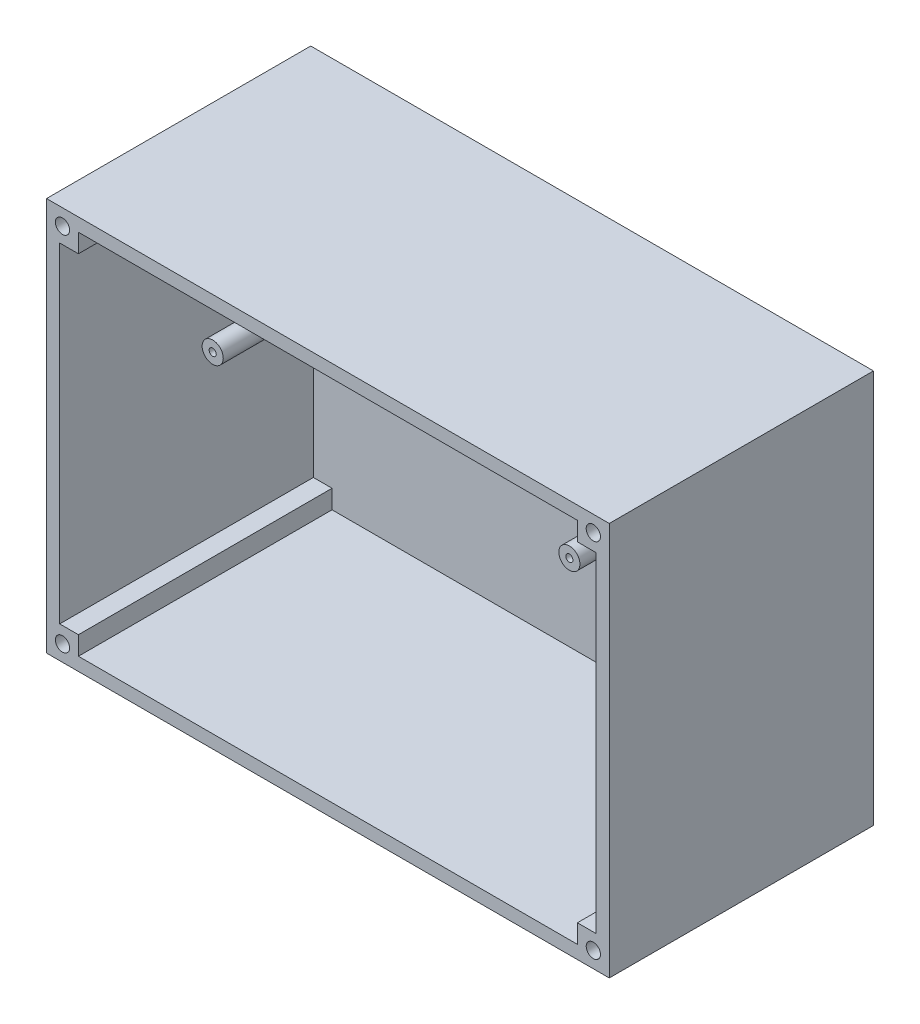
SolidWorks part; units mm, degrees
ref_plane "Płaszczyzna przednia" through (0, 0, 0) normal (0, 0, 1) x (1, 0, 0)
ref_plane "Płaszczyzna górna" through (0, 0, 0) normal (0, 1, 0) x (1, 0, 0)
ref_plane "Płaszczyzna prawa" through (0, 0, 0) normal (1, 0, 0) x (0, 0, -1)
sketch "Szkic4" plane through (0, 0, 0) normal (0, 0, 1) x (-1, 0, 0)
  line L26 (-171.4939, -76.4107) -> (31.5061, -76.4107)
  line L30 (-171.4939, -76.4107) -> (-171.4939, 62.5893)
  line L34 (31.5061, 0) -> (31.5061, -76.4107)
  line L35 (31.5061, 0) -> (31.5061, 62.5893)
  line L36 (31.5061, 62.5893) -> (-171.4939, 62.5893)
  point P86 (-69.4627, -6.9107)
sketch "Szkic5" plane through (0, 0, 0) normal (0, 0, 1) x (-1, 0, 0)
  line L26 (-171.4939, -76.4107) -> (31.5061, -76.4107)
  line L30 (-171.4939, -76.4107) -> (-171.4939, 62.5893)
  line L33 (30.0061, 0) -> (31.5061, 0)
  line L34 (31.5061, 0) -> (31.5061, -76.4107)
  line L35 (31.5061, 0) -> (31.5061, 62.5893)
  line L36 (31.5061, 62.5893) -> (-171.4939, 62.5893)
  line L37 (-176.4939, 67.5893) -> (36.5061, 67.5893)
  line L38 (36.5061, 67.5893) -> (36.5061, -81.4107)
  line L39 (36.5061, -81.4107) -> (-176.4939, -81.4107)
  line L40 (-176.4939, -81.4107) -> (-176.4939, 67.5893)
  circle A0 centre (-154.7539, 47.5493) radius 1.35
  circle A1 centre (-154.7539, -0.7107) radius 1.35
  circle A2 centre (-103.9539, 14.5293) radius 1.35
  circle A3 centre (-103.9539, 42.4693) radius 1.35
  circle A12 centre (-149.9208, -27.9486) radius 1.35
  circle A13 centre (-149.9208, -54.9486) radius 1.35
  circle A14 centre (-149.9208, -27.9486) radius 3.5
  circle A15 centre (-149.9208, -54.9486) radius 3.5
  circle A16 centre (-154.7539, -0.7107) radius 3.5
  circle A17 centre (-154.7539, 47.5493) radius 3.5
  circle A18 centre (-103.9539, 42.4693) radius 3.5
  circle A19 centre (-103.9539, 14.5293) radius 3.5
  circle A28 centre (-121.3881, -22.5) radius 4
  circle A29 centre (-121.3881, -22.5) radius 1.35
  circle A30 centre (-121.3881, -69.5) radius 1.35
  circle A31 centre (-121.3881, -69.5) radius 4
  circle A32 centre (13.6119, -22.5) radius 1.35
  circle A33 centre (13.6119, -69.5) radius 1.35
  circle A34 centre (13.6119, -69.5) radius 4
  circle A35 centre (13.6119, -22.5) radius 4
  point P1 (0, 0)
  point P86 (-69.4627, -6.9107)
  dimension "D2" = 2.7
  dimension "D3" = 2.7
  dimension "D6" = 2.7
  dimension "D7" = 2.7
  dimension "D8" = 2.7
  dimension "D9" = 2.7
  dimension "D10" = 2.7
  dimension "D11" = 2.7
  dimension "D12" = 2.7
  dimension "D13" = 2.7
  dimension "D14" = 7
  dimension "D15" = 7
  dimension "D16" = 7
  dimension "D17" = 7
  dimension "D18" = 8
  dimension "D19" = 8
  dimension "D20" = 8
  dimension "D21" = 8
  dimension "D22" = 7
  dimension "D23" = 7
  dimension "D33" = 213
  dimension "D34" = 149
extrude "Dodanie-wyciągnięcie1" add sketch "Szkic5" along normal blind 100 contours L40 L39 L38 L37 L36 L35 L34 L26 L30 region at (69.9939, -64.9899, 0)
extrude "Dodanie-wyciągnięcie2" add sketch "Szkic4" along normal blind 4
sketch "Szkic7" plane through (0, 0, 0) normal (0, 0, 1) x (-1, 0, 0)
  line L26 (-171.4939, -76.4107) -> (31.5061, -76.4107)
  line L30 (-171.4939, -76.4107) -> (-171.4939, 62.5893)
  line L33 (30.0061, 0) -> (31.5061, 0)
  line L34 (31.5061, 0) -> (31.5061, -76.4107)
  line L35 (31.5061, 0) -> (31.5061, 62.5893)
  line L36 (31.5061, 62.5893) -> (-171.4939, 62.5893)
  line L37 (-176.4939, 67.5893) -> (36.5061, 67.5893)
  line L38 (36.5061, 67.5893) -> (36.5061, -81.4107)
  line L39 (36.5061, -81.4107) -> (-176.4939, -81.4107)
  line L40 (-176.4939, -81.4107) -> (-176.4939, 67.5893)
  circle A0 centre (-154.7539, 47.5493) radius 1.35
  circle A1 centre (-154.7539, -0.7107) radius 1.35
  circle A2 centre (-103.9539, 14.5293) radius 1.35
  circle A3 centre (-103.9539, 42.4693) radius 1.35
  circle A4 centre (-83.3982, 52.9593) radius 1.35
  circle A5 centre (-40.2182, 52.9593) radius 1.35
  circle A6 centre (-83.3982, -5.4607) radius 1.35
  circle A7 centre (-40.2182, -5.4607) radius 1.35
  circle A8 centre (-27.0516, 13.6107) radius 1
  circle A9 centre (-27.0516, -5.3893) radius 1
  circle A10 centre (-18.0313, 31.2757) radius 1
  circle A11 centre (2.9687, 31.2757) radius 1
  circle A12 centre (-149.9208, -27.9486) radius 1.35
  circle A13 centre (-149.9208, -54.9486) radius 1.35
  circle A14 centre (-149.9208, -27.9486) radius 3.5
  circle A15 centre (-149.9208, -54.9486) radius 3.5
  circle A16 centre (-154.7539, -0.7107) radius 3.5
  circle A17 centre (-154.7539, 47.5493) radius 3.5
  circle A18 centre (-103.9539, 42.4693) radius 3.5
  circle A19 centre (-103.9539, 14.5293) radius 3.5
  circle A20 centre (-83.3982, 52.9593) radius 3.5
  circle A21 centre (-40.2182, 52.9593) radius 3.5
  circle A22 centre (-83.3982, -5.4607) radius 3.5
  circle A23 centre (-40.2182, -5.4607) radius 3.5
  circle A24 centre (-18.0313, 31.2757) radius 3.5
  circle A25 centre (2.9687, 31.2757) radius 3.5
  circle A26 centre (-27.0516, 13.6107) radius 3.5
  circle A27 centre (-27.0516, -5.3893) radius 3.5
  circle A28 centre (-121.3881, -22.5) radius 4
  circle A29 centre (-121.3881, -22.5) radius 1.35
  circle A30 centre (-121.3881, -69.5) radius 1.35
  circle A31 centre (-121.3881, -69.5) radius 4
  circle A32 centre (13.6119, -22.5) radius 1.35
  circle A33 centre (13.6119, -69.5) radius 1.35
  circle A34 centre (13.6119, -69.5) radius 4
  circle A35 centre (13.6119, -22.5) radius 4
  point P86 (-69.4627, -6.9107)
  dimension "D1" = 2.7
  dimension "D2" = 2.7
  dimension "D3" = 2.7
  dimension "D4" = 2.7
  dimension "D5" = 2.7
  dimension "D6" = 2.7
  dimension "D7" = 2.7
  dimension "D8" = 2.7
  dimension "D9" = 2.7
  dimension "D10" = 2.7
  dimension "D11" = 2.7
  dimension "D12" = 2.7
  dimension "D13" = 2.7
  dimension "D14" = 7
  dimension "D15" = 7
  dimension "D16" = 7
  dimension "D17" = 7
  dimension "D18" = 8
  dimension "D19" = 8
  dimension "D20" = 8
  dimension "D21" = 8
  dimension "D22" = 7
  dimension "D23" = 7
  dimension "D24" = 7
  dimension "D25" = 2.7
  dimension "D26" = 7
  dimension "D27" = 7
  dimension "D28" = 7
  dimension "D29" = 7
  dimension "D30" = 7
  dimension "D31" = 7
  dimension "D32" = 7
  dimension "D33" = 213
  dimension "D34" = 149
extrude "Dodanie-wyciągnięcie3" add sketch "Szkic7" along normal blind 60 contours A34 A33 | A35 A32 | A31 A30 | A28 A29 region at (125.2749, 22.5, 0) region at (125.2749, 69.5, 0) region at (-9.7251, 69.5, 0) region at (-9.7251, 22.5, 0)
sketch "Szkic8" plane through (0, 0, 0) normal (0, 0, 1) x (-1, 0, 0)
  line L26 (-171.4939, -76.4107) -> (31.5061, -76.4107)
  line L30 (-171.4939, -76.4107) -> (-171.4939, 62.5893)
  line L33 (30.0061, 0) -> (31.5061, 0)
  line L34 (31.5061, 0) -> (31.5061, -76.4107)
  line L35 (31.5061, 0) -> (31.5061, 62.5893)
  line L36 (31.5061, 62.5893) -> (-171.4939, 62.5893)
  line L37 (-176.4939, 67.5893) -> (36.5061, 67.5893)
  line L38 (36.5061, 67.5893) -> (36.5061, -81.4107)
  line L39 (36.5061, -81.4107) -> (-176.4939, -81.4107)
  line L40 (-176.4939, -81.4107) -> (-176.4939, 67.5893)
  circle A0 centre (-154.7539, 47.5493) radius 1.35
  circle A1 centre (-154.7539, -0.7107) radius 1.35
  circle A2 centre (-103.9539, 14.5293) radius 1.35
  circle A3 centre (-103.9539, 42.4693) radius 1.35
  circle A12 centre (-149.9208, -27.9486) radius 1.35
  circle A13 centre (-149.9208, -54.9486) radius 1.35
  circle A14 centre (-149.9208, -27.9486) radius 3.5
  circle A15 centre (-149.9208, -54.9486) radius 3.5
  circle A16 centre (-154.7539, -0.7107) radius 3.5
  circle A17 centre (-154.7539, 47.5493) radius 3.5
  circle A18 centre (-103.9539, 42.4693) radius 3.5
  circle A19 centre (-103.9539, 14.5293) radius 3.5
  circle A28 centre (-121.3881, -22.5) radius 4
  circle A29 centre (-121.3881, -22.5) radius 1.35
  circle A30 centre (-121.3881, -69.5) radius 1.35
  circle A31 centre (-121.3881, -69.5) radius 4
  circle A32 centre (13.6119, -22.5) radius 1.35
  circle A33 centre (13.6119, -69.5) radius 1.35
  circle A34 centre (13.6119, -69.5) radius 4
  circle A35 centre (13.6119, -22.5) radius 4
  point P86 (-69.4627, -6.9107)
  dimension "D2" = 2.7
  dimension "D3" = 2.7
  dimension "D6" = 2.7
  dimension "D7" = 2.7
  dimension "D8" = 2.7
  dimension "D9" = 2.7
  dimension "D10" = 2.7
  dimension "D11" = 2.7
  dimension "D12" = 2.7
  dimension "D13" = 2.7
  dimension "D14" = 7
  dimension "D15" = 7
  dimension "D16" = 7
  dimension "D17" = 7
  dimension "D18" = 8
  dimension "D19" = 8
  dimension "D20" = 8
  dimension "D21" = 8
  dimension "D22" = 7
  dimension "D23" = 7
  dimension "D33" = 213
  dimension "D34" = 149
extrude "Dodanie-wyciągnięcie4" add sketch "Szkic8" along normal blind 15 contours A15 A13 | A14 A12 | A16 A1 | A17 A0 | A18 A3 | A19 A2 region at (153.3218, 27.9486, 0) region at (153.3218, 54.9486, 0) region at (158.1549, 0.7107, 0) region at (158.1549, -47.5493, 0) region at (107.3549, -42.4693, 0) region at (107.3549, -14.5293, 0)
sketch "Szkic11" plane through (0, 0, 0) normal (0, 0, 1) x (-1, 0, 0)
  line L23 (-176.4939, -81.4107) -> (-164.4229, -81.4107)
  line L26 (-171.4939, -76.4107) -> (31.5061, -76.4107)
  line L30 (-171.4939, -76.4107) -> (-171.4939, 62.5893)
  line L31 (-176.4939, -81.4107) -> (-176.4939, -69.3396)
  line L32 (-176.4939, -69.3396) -> (-164.4229, -69.3396)
  line L33 (30.0061, 0) -> (31.5061, 0)
  line L34 (31.5061, 0) -> (31.5061, -76.4107)
  line L35 (31.5061, 0) -> (31.5061, 62.5893)
  line L36 (31.5061, 62.5893) -> (-171.4939, 62.5893)
  line L37 (-176.4939, 67.5893) -> (36.5061, 67.5893)
  line L38 (36.5061, 67.5893) -> (36.5061, -81.4107)
  line L39 (36.5061, -81.4107) -> (-176.4939, -81.4107)
  line L40 (-176.4939, -81.4107) -> (-176.4939, 67.5893)
  line L41 (-164.4229, -81.4107) -> (-164.4229, -69.3396)
  line L42 (-176.4939, 67.5893) -> (-164.4229, 67.5893)
  line L43 (-176.4939, 67.5893) -> (-176.4939, 55.5183)
  line L44 (-176.4939, 55.5183) -> (-164.4229, 55.5183)
  line L45 (-164.4229, 67.5893) -> (-164.4229, 55.5183)
  line L46 (36.5061, 67.5893) -> (24.435, 67.5893)
  line L47 (36.5061, 67.5893) -> (36.5061, 55.5183)
  line L48 (36.5061, 55.5183) -> (24.435, 55.5183)
  line L49 (24.435, 67.5893) -> (24.435, 55.5183)
  line L50 (36.5061, -81.4107) -> (24.435, -81.4107)
  line L51 (36.5061, -81.4107) -> (36.5061, -69.3396)
  line L52 (36.5061, -69.3396) -> (24.435, -69.3396)
  line L53 (24.435, -81.4107) -> (24.435, -69.3396)
  circle A0 centre (-154.7539, 47.5493) radius 1.35
  circle A1 centre (-154.7539, -0.7107) radius 1.35
  circle A2 centre (-103.9539, 14.5293) radius 1.35
  circle A3 centre (-103.9539, 42.4693) radius 1.35
  circle A4 centre (-83.3982, 52.9593) radius 1.35
  circle A5 centre (-40.2182, 52.9593) radius 1.35
  circle A6 centre (-83.3982, -5.4607) radius 1.35
  circle A7 centre (-40.2182, -5.4607) radius 1.35
  circle A8 centre (-27.0516, 13.6107) radius 1
  circle A9 centre (-27.0516, -5.3893) radius 1
  circle A10 centre (-18.0313, 31.2757) radius 1
  circle A11 centre (2.9687, 31.2757) radius 1
  circle A12 centre (-149.9208, -27.9486) radius 1.35
  circle A13 centre (-149.9208, -54.9486) radius 1.35
  circle A14 centre (-149.9208, -27.9486) radius 3.5
  circle A15 centre (-149.9208, -54.9486) radius 3.5
  circle A16 centre (-154.7539, -0.7107) radius 3.5
  circle A17 centre (-154.7539, 47.5493) radius 3.5
  circle A18 centre (-103.9539, 42.4693) radius 3.5
  circle A19 centre (-103.9539, 14.5293) radius 3.5
  circle A20 centre (-83.3982, 52.9593) radius 3.5
  circle A21 centre (-40.2182, 52.9593) radius 3.5
  circle A22 centre (-83.3982, -5.4607) radius 3.5
  circle A23 centre (-40.2182, -5.4607) radius 3.5
  circle A24 centre (-18.0313, 31.2757) radius 3.5
  circle A25 centre (2.9687, 31.2757) radius 3.5
  circle A26 centre (-27.0516, 13.6107) radius 3.5
  circle A27 centre (-27.0516, -5.3893) radius 3.5
  circle A28 centre (-121.3881, -22.5) radius 4
  circle A29 centre (-121.3881, -22.5) radius 1.35
  circle A30 centre (-121.3881, -69.5) radius 1.35
  circle A31 centre (-121.3881, -69.5) radius 4
  circle A32 centre (13.6119, -22.5) radius 1.35
  circle A33 centre (13.6119, -69.5) radius 1.35
  circle A34 centre (13.6119, -69.5) radius 4
  circle A35 centre (13.6119, -22.5) radius 4
  point P86 (-69.4627, -6.9107)
  dimension "D1" = 2.7
  dimension "D2" = 2.7
  dimension "D3" = 2.7
  dimension "D4" = 2.7
  dimension "D5" = 2.7
  dimension "D6" = 2.7
  dimension "D7" = 2.7
  dimension "D8" = 2.7
  dimension "D9" = 2.7
  dimension "D10" = 2.7
  dimension "D11" = 2.7
  dimension "D12" = 2.7
  dimension "D13" = 2.7
  dimension "D14" = 7
  dimension "D15" = 7
  dimension "D16" = 7
  dimension "D17" = 7
  dimension "D18" = 8
  dimension "D19" = 8
  dimension "D20" = 8
  dimension "D21" = 8
  dimension "D22" = 7
  dimension "D23" = 7
  dimension "D24" = 7
  dimension "D25" = 2.7
  dimension "D26" = 7
  dimension "D27" = 7
  dimension "D28" = 7
  dimension "D29" = 7
  dimension "D30" = 7
  dimension "D31" = 7
  dimension "D32" = 7
  dimension "D33" = 213
  dimension "D34" = 149
extrude "Dodanie-wyciągnięcie5" add sketch "Szkic11" along normal up to surface (100 mm away) contours L45 L36 L30 L44 | L53 L26 L34 L52 | L36 L49 L48 L35 | L26 L41 L32 L30 region at (167.9584, 72.8751, 0) region at (-27.9705, 72.8751, 0) region at (167.9584, -59.0538, 0) region at (-27.9705, -59.0538, 0) up to face at (69.9939, 6.9107, 100)
sketch "Szkic12" plane through (0, 0, 100) normal (0, 0, 1) x (1, 0, 0)
  line L1 (-24.435, 69.3396) -> (-36.5061, 69.3396)
  line L2 (-24.435, 69.3396) -> (-24.435, 81.4107)
  line L3 (-24.435, 81.4107) -> (-36.5061, 81.4107)
  line L4 (-36.5061, 69.3396) -> (-36.5061, 81.4107)
  line L5 (-24.435, -55.5183) -> (-36.5061, -55.5183)
  line L6 (-24.435, -55.5183) -> (-24.435, -67.5893)
  line L7 (-24.435, -67.5893) -> (-36.5061, -67.5893)
  line L8 (-36.5061, -55.5183) -> (-36.5061, -67.5893)
  line L9 (164.4229, -55.5183) -> (176.4939, -55.5183)
  line L10 (164.4229, -55.5183) -> (164.4229, -67.5893)
  line L11 (164.4229, -67.5893) -> (176.4939, -67.5893)
  line L12 (176.4939, -55.5183) -> (176.4939, -67.5893)
  line L13 (176.4939, 81.4107) -> (164.4229, 81.4107)
  line L14 (176.4939, 81.4107) -> (176.4939, 69.3396)
  line L15 (176.4939, 69.3396) -> (164.4229, 69.3396)
  line L16 (164.4229, 81.4107) -> (164.4229, 69.3396)
  circle A0 centre (-30.4705, 75.3751) radius 2.7
  circle A1 centre (-30.4705, -61.5538) radius 2.7
  circle A2 centre (170.4584, -61.5538) radius 2.7
  circle A3 centre (170.4584, 75.3751) radius 2.7
extrude "Wytnij-wyciągnięcie10" cut sketch "Szkic12" against normal blind 50 contours A0 | A1 | A2 | A3
sketch "Szkic14" plane through (0, 0, 4) normal (0, 0, 1) x (1, 0, 0)
  text T0 "AquariumBox\r\n         by\r\nBaartek57548" font "Franklin Gothic Medium Cond" height 5
extrude "Wytnij-wyciągnięcie11" cut sketch "Szkic14" along direction (0, 0, -1) on the side against the normal blind 1
